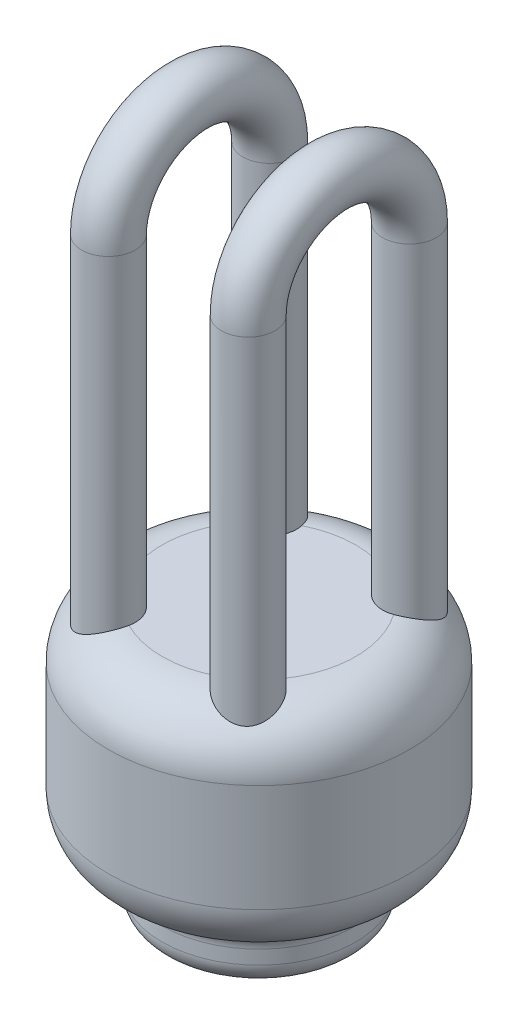
SolidWorks part; units mm, degrees
ref_plane "前视基准面" through (0, 0, 0) normal (0, 0, 1) x (1, 0, 0)
ref_plane "上视基准面" through (0, 0, 0) normal (0, 1, 0) x (1, 0, 0)
ref_plane "右视基准面" through (0, 0, 0) normal (1, 0, 0) x (0, 0, -1)
sketch "草图1" plane through (0, 0, 0) normal (0, 1, 0) x (1, 0, 0)
  circle A0 centre (0, 0) radius 28
  dimension "D1" = 56
extrude "凸台-拉伸1" add sketch "草图1" along normal blind 40
ref_plane "基准面1" through (13, 0, 0) normal (1, 0, 0) x (0, 0, -1)
sketch "草图2" plane through (13, 0, 0) normal (1, 0, 0) x (0, 0, -1)
  line L0 (0, 0) -> (0, 98.4092) construction
  line L1 (15, 100) -> (15, 40)
  line L2 (28, 40) -> (-28, 40) construction
  line L3 (-15, 100) -> (-15, 40)
  arc A0 (15, 100) -> (-15, 100) centre (0, 100) ccw
  dimension "D1" = 30
  dimension "D2" = 60
sweep "扫描1" add path "草图2" circular profile diameter 10 parameters "D3"=10
mirror "镜向1" about plane through (0, 0, 0) normal (1, 0, 0) of "扫描1"
sketch "草图13" plane through (0, 0, 0) normal (0, -1, 0) x (1, 0, 0)
  circle A0 centre (0, 0) radius 18
  dimension "D1" = 36
extrude "凸台-拉伸2" add sketch "草图13" along normal blind 10 contours A0
fillet "圆角1" radius 10 2 edges at (0, 0, 28) (0, 40, 28)
fillet "圆角2" radius 4 2 edges at (0, 0, -18) (0, -10, -18)
